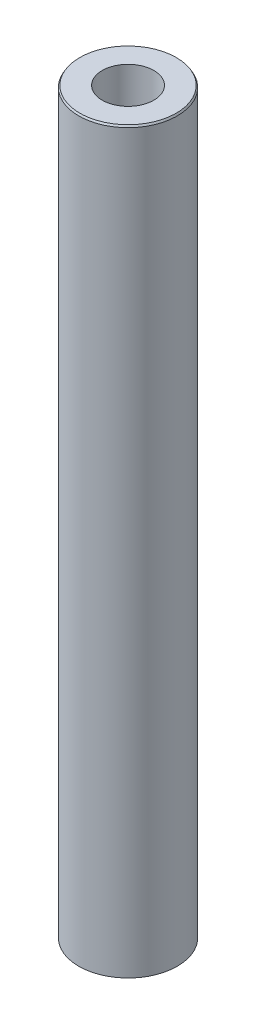
SolidWorks part; units mm, degrees
ref_plane "Front Plane" through (0, 0, 0) normal (0, 0, 1) x (1, 0, 0)
ref_plane "Top Plane" through (0, 0, 0) normal (0, 1, 0) x (1, 0, 0)
ref_plane "Right Plane" through (0, 0, 0) normal (1, 0, 0) x (0, 0, -1)
sketch "Sketch1" plane through (0, 0, 0) normal (0, 1, 0) x (1, 0, 0)
  circle A0 centre (0, 0) radius 40
  dimension "SHAFT_OD" = 80
extrude "Boss-Extrude1" add sketch "Sketch1" along normal blind 600
sketch "Sketch2" plane through (0, 0, 0) normal (0, 1, 0) x (1, 0, 0)
  circle A0 centre (0, 0) radius 20.9355
  dimension "BORE_D" = 41.871
extrude "Cut-Extrude1" cut sketch "Sketch2" along normal through all
chamfer "Chamfer1" distance 1.4752 angle 30 2 edges at (0, 600, 40) (0, 0, 40) first distance on face at (0, 600, 40) first distance on face at (0, 0, 20.9355)
